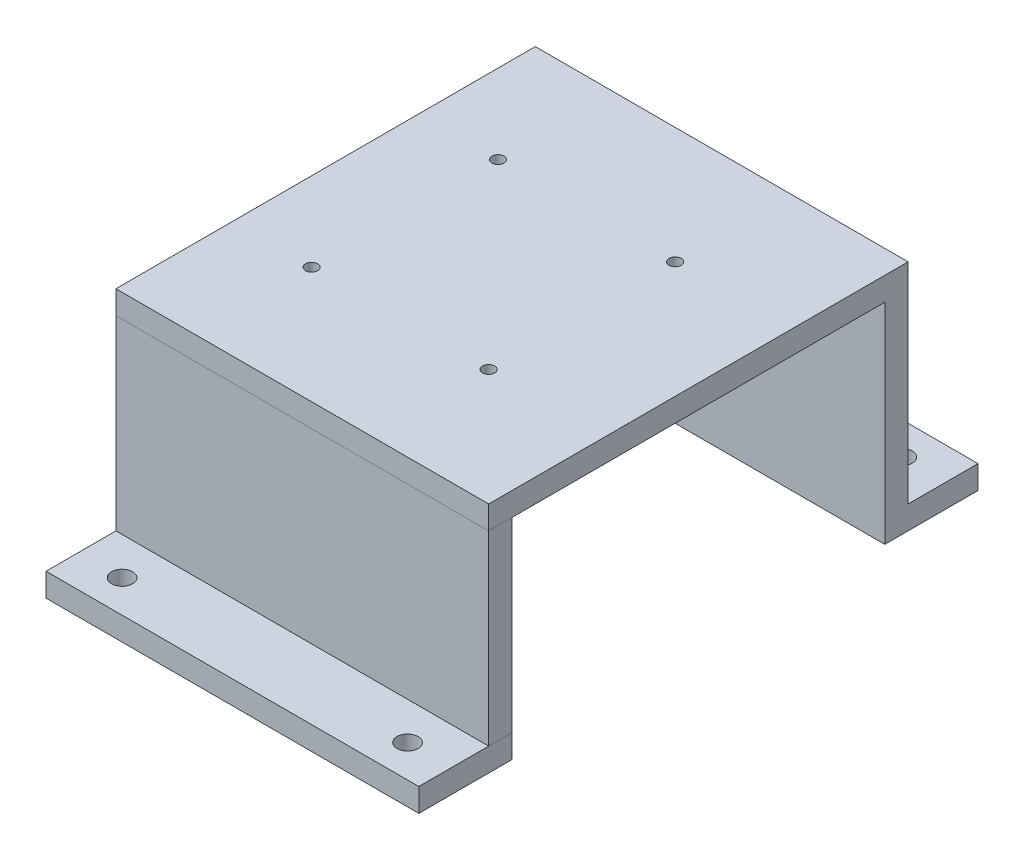
SolidWorks part; units mm, degrees
ref_plane "Front Plane" through (0, 0, 0) normal (0, 0, 1) x (1, 0, 0)
ref_plane "Top Plane" through (0, 0, 0) normal (0, 1, 0) x (1, 0, 0)
ref_plane "Right Plane" through (0, 0, 0) normal (1, 0, 0) x (0, 0, -1)
sketch "Sketch1" plane through (0, 0, 0) normal (0, 1, 0) x (1, 0, 0)
  line L0 (0, 0) -> (0, 60) construction
  line L1 (-40, 60) -> (40, 60)
  line L2 (-40, 60) -> (-40, 40)
  line L3 (-40, 40) -> (40, 40)
  line L4 (40, 60) -> (40, 40)
  line L5 (0, 0) -> (-30.625, 53.0441) construction
  line L6 (-55, 0) -> (55, 0) construction
  line L7 (40, -60) -> (40, -40)
  line L8 (-40, -40) -> (40, -40)
  line L9 (-40, -60) -> (-40, -40)
  line L10 (-40, -60) -> (40, -60)
  circle A0 centre (-30.625, 53.0441) radius 2.25
  circle A1 centre (30.625, 53.0441) radius 2.25
  circle A2 centre (30.625, -53.0441) radius 2.25
  circle A3 centre (-30.625, -53.0441) radius 2.25
  point P9 (0, 0)
  point P12 (0, 0)
  dimension "D7" = 4.5
  dimension "D1" = 40
  dimension "D2" = 20
  dimension "D3" = 80
  dimension "D4" = 40
  dimension "D5" = 61.25
  dimension "D6" = 30
extrude "Boss-Extrude1" add sketch "Sketch1" along normal blind 5
sketch "Sketch2" plane through (0, 5, 0) normal (0, 1, 0) x (1, 0, 0)
  line L0 (40, 40) -> (40, 60) construction
  line L1 (-40, 40) -> (40, 40)
  line L2 (-40, 40) -> (-40, 45)
  line L3 (-40, 45) -> (40, 45)
  line L4 (40, 40) -> (40, 45)
  line L5 (-2.75, 0) -> (2.75, 0) construction
  line L6 (40, -40) -> (40, -45)
  line L7 (-40, -45) -> (40, -45)
  line L8 (-40, -40) -> (-40, -45)
  line L9 (-40, -40) -> (40, -40)
  point P5 (0, 0)
  point P7 (0, 0)
  point P8 (0, 0)
  point P9 (-39.6643, 48.4989)
  point P10 (-39.4167, 51.9162)
  point P13 (0, 0)
  dimension "D1" = 5
extrude "Boss-Extrude2" add sketch "Sketch2" along normal blind 40
sketch "Sketch3" plane through (0, 45, 0) normal (0, 1, 0) x (1, 0, 0)
  line L1 (-40, 45) -> (40, 45)
  line L2 (-40, 45) -> (-40, -45)
  line L3 (-40, -45) -> (40, -45)
  line L4 (40, 45) -> (40, -45)
  dimension "D1" = 90
  dimension "D2" = 80
extrude "Boss-Extrude3" add sketch "Sketch3" along normal blind 5 contours L2 L3 L4 L1
sketch "Sketch4" plane through (0, 50, 0) normal (0, 1, 0) x (1, 0, 0)
  line L1 (-23, 20) -> (15, 20) construction
  line L2 (-23, 20) -> (-23, -20) construction
  line L3 (-23, -20) -> (15, -20) construction
  line L4 (15, 20) -> (15, -20) construction
  circle A0 centre (-23, 20) radius 1.3
  circle A1 centre (15, 20) radius 1.3
  circle A2 centre (15, -20) radius 1.3
  circle A3 centre (-23, -20) radius 1.3
  dimension "D5" = 2.6
  dimension "D1" = 23
  dimension "D2" = 40
  dimension "D3" = 38
  dimension "D4" = 20
extrude "Cut-Extrude1" cut sketch "Sketch4" against normal up to next (5 mm away)
